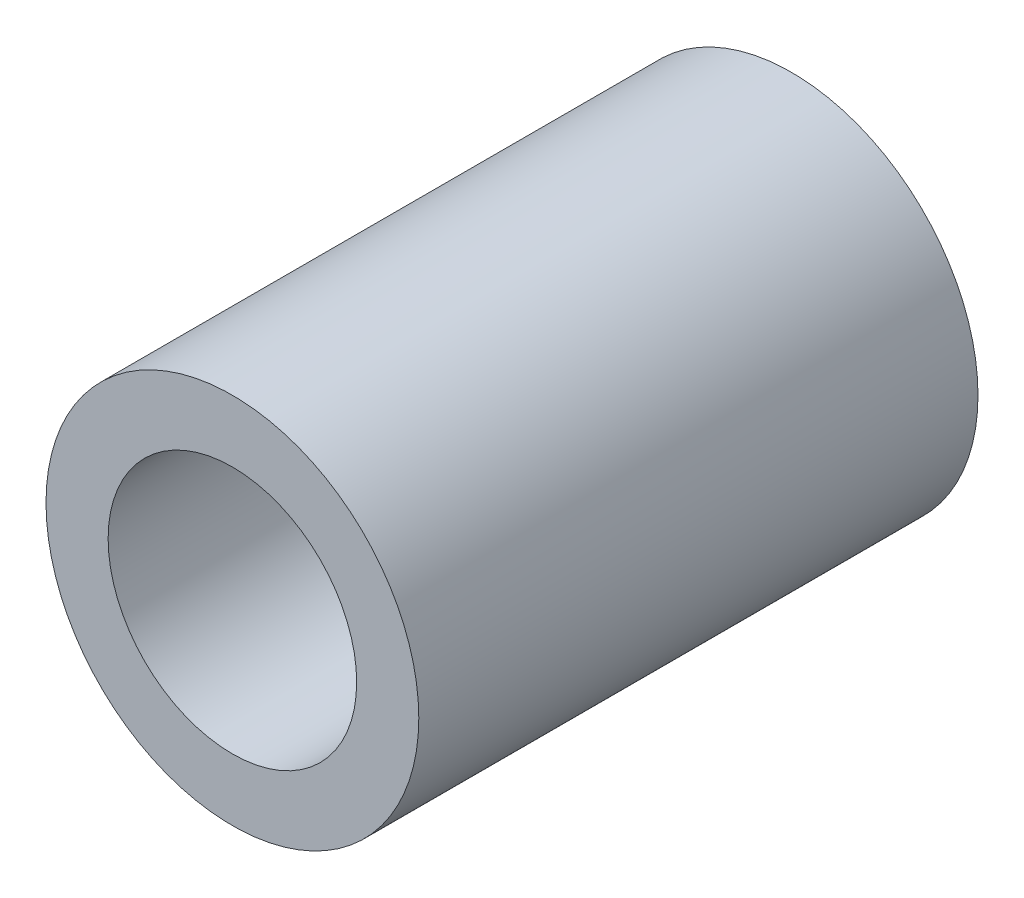
SolidWorks part; units mm, degrees
ref_plane "前视基准面" through (0, 0, 0) normal (0, 0, 1) x (1, 0, 0)
ref_plane "上视基准面" through (0, 0, 0) normal (0, 1, 0) x (1, 0, 0)
ref_plane "右视基准面" through (0, 0, 0) normal (1, 0, 0) x (0, 0, -1)
sketch "草图1" plane through (0, 0, 0) normal (0, 0, 1) x (1, 0, 0)
  circle A0 centre (0, 0) radius 3
extrude "凸台-拉伸1" add sketch "草图1" along normal blind 10
sketch "草图2" plane through (0, 0, 10) normal (0, 0, 1) x (1, 0, 0)
  circle A0 centre (0, 0) radius 2
extrude "切除-拉伸1" cut sketch "草图2" against normal blind 9
hole_wizard "大小mm 暗销孔2" positions "草图7" profile "草图8" hole size "Ø2.0" standard "GB" end condition through all
sketch "草图7" plane through (0, 0, 1) normal (0, 0, 1) x (1, 0, 0)
  point P0 (0, 0)
sketch "草图8" plane through (0, 0, 1) normal (1, 0, 0) x (0, -1, 0)
  line L0 (0, 0) -> (0, 1)
  line L1 (0, 1) -> (1, 1)
  line L2 (1, 1) -> (1, 0.025)
  line L3 (1, 0.025) -> (1.025, 0)
  line L5 (1.025, 0) -> (0, 0)
  line L6 (-1, 0.025) -> (-1.025, 0) construction
  line L11 (0, -6.35) -> (0, 107.95) construction
  dimension "通孔孔直径" = 2
  dimension "通孔孔深度" = 1
  dimension "近端锥形沉头孔直径" = 2.05
  dimension "近端锥形沉头孔角度" = 90
sketch "草图10" plane through (0, 0, 10) normal (0, 0, 1) x (1, 0, 0)
  circle A1 centre (0, 0) radius 3
  circle A2 centre (0, 0) radius 3
  dimension "D1" = 0
extrude "切除-拉伸2" cut sketch "草图10" against normal blind 1
